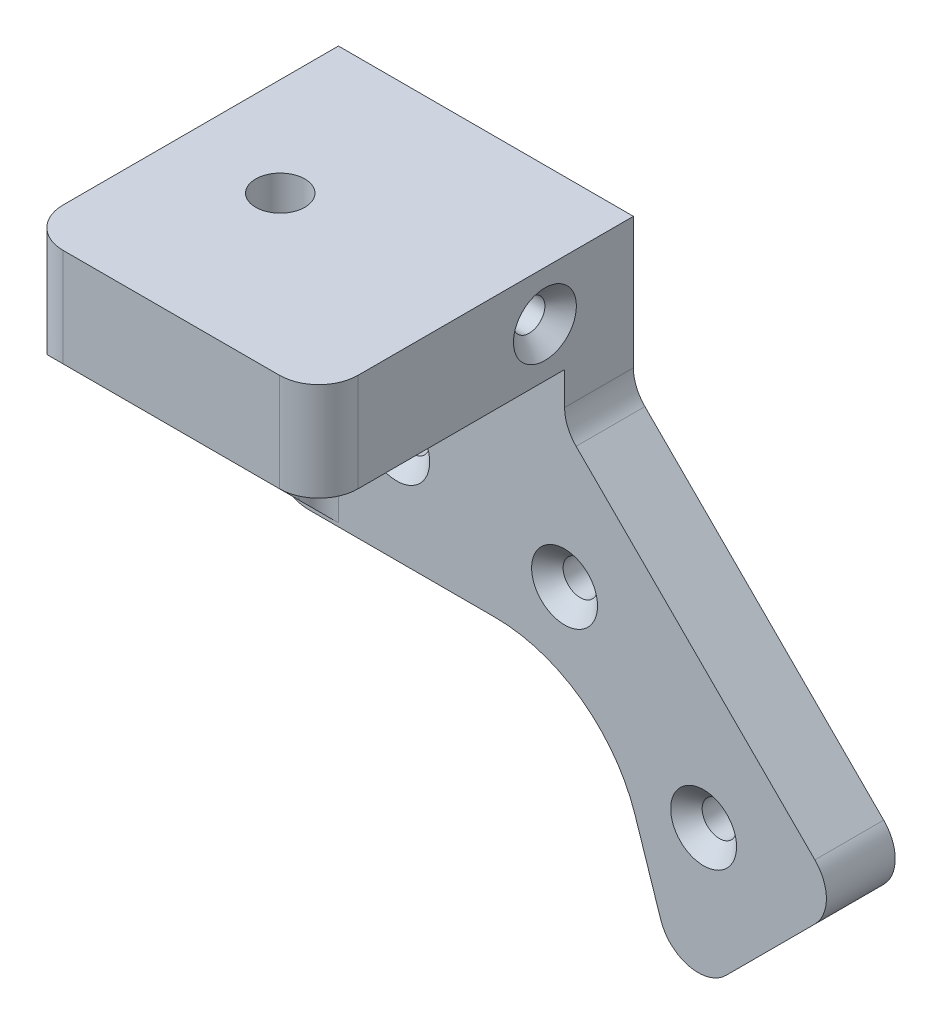
SolidWorks part; units mm, degrees
ref_plane "Front Plane" through (0, 0, 0) normal (0, 0, 1) x (1, 0, 0)
ref_plane "Top Plane" through (0, 0, 0) normal (0, 1, 0) x (1, 0, 0)
ref_plane "Right Plane" through (0, 0, 0) normal (1, 0, 0) x (0, 0, -1)
sketch "Sketch1" plane through (0, 0, 0) normal (0, 0, 1) x (1, 0, 0)
  line L0 (15, 27.5) -> (15, 12.5)
  line L5 (-15, 27.5) -> (15, 27.5)
  line L6 (-15, 27.5) -> (-15, -27.5)
  line L7 (-15, -27.5) -> (15, -27.5)
  line L9 (15, 12.5) -> (43.2843, -15.7843)
  line L10 (-15, -27.5) -> (15, 27.5) construction
  line L11 (43.2843, -15.7843) -> (23.2843, -35.7843)
  line L12 (23.2843, -35.7843) -> (15, -27.5)
  point P0 (0, 0)
  dimension "D1" = 45
  dimension "D2" = 55
  dimension "D3" = 30
  dimension "D4" = 40
  dimension "D5" = 15
extrude "Boss-Extrude1" add sketch "Sketch1" along normal blind 5 and the other way blind 2
sketch "Sketch3" plane through (0, 0, 5) normal (0, 0, 1) x (1, 0, 0)
  line L0 (15, 12.5) -> (15, 27.5) construction
  line L1 (-15, 27.5) -> (15, 27.5)
  line L2 (-15, 27.5) -> (-15, 17.5)
  line L3 (-15, 17.5) -> (15, 17.5)
  line L4 (15, 27.5) -> (15, 17.5)
  dimension "D1" = 10
extrude "Boss-Extrude2" add sketch "Sketch3" along normal blind 25
sketch "Sketch4" plane through (0, 27.5, 0) normal (0, 1, 0) x (1, 0, 0)
  line L0 (-15, -30) -> (-15, 2) construction
  line L1 (15, -30) -> (-15, -30) construction
  line L2 (15, -30) -> (15, -5) construction
  line L3 (15, -5) -> (-15, -5) construction
  line L4 (-15, -30) -> (-15, -5) construction
  line L5 (15, -30) -> (15, 2) construction
  line L6 (-15, 2) -> (15, 2) construction
  line L7 (-15, 2) -> (-15, 7) construction
  line L8 (-15, 7) -> (15, 7) construction
  line L9 (15, 2) -> (15, 7) construction
  line L10 (15, -20.575) -> (-15, -20.575) construction
  circle A0 centre (-5, -13.9175) radius 2.5
  circle A1 centre (-5, -13.9175) radius 6.6575 construction
  circle A2 centre (-5, -14.15) radius 6.425 construction
  dimension "D3" = 13.315
  dimension "D4" = 5
  dimension "D7" = 21.15
  dimension "D8" = 12.85
  dimension "D1" = 25
  dimension "D2" = 5
  dimension "D6" = 20
extrude "Cut-Extrude1" cut sketch "Sketch4" against normal through all
sketch "Sketch6" plane through (-15, 0, 0) normal (-1, 0, 0) x (0, 0, 1)
  line L0 (30, 17.5) -> (5, -7.5)
  line L1 (5, 17.5) -> (5, -27.5) construction
  dimension "D1" = 45
rib "Rib1" sketch "Sketch6" sketch "Sketch6" thickness 5 extrusion direction parallel to sketch draft on no parameters "D1"=5
sketch "Sketch7" plane through (0, 0, 5) normal (0, 0, 1) x (1, 0, 0)
  line L0 (22.1747, -18.1589) -> (26.8198, -32.2487)
  line L1 (-15, -7.8553) -> (7.9289, -7.8553)
  line L2 (-15, -7.8553) -> (-15, -27.5)
  line L3 (-15, -7.5) -> (-15, -27.5) construction
  line L4 (-15, -27.5) -> (15, -27.5) construction
  line L5 (15, 27.5) -> (-15, 27.5) construction
  line L6 (23.2843, -35.7843) -> (43.2843, -15.7843) construction
  line L7 (-15, -27.5) -> (23.2843, -35.7843)
  line L8 (23.2843, -35.7843) -> (26.8198, -32.2487)
  arc A0 (22.1747, -18.1589) -> (7.9289, -7.8553) centre (7.9289, -22.8553) ccw
  circle A1 centre (7.9289, -22.8553) radius 14 construction
  dimension "D1" = 1
  dimension "D2" = 5
extrude "Cut-Extrude2" cut sketch "Sketch7" against normal up to vertex (7 mm away) up to point (-15, -27.5, -2)
sketch "Sketch8" plane through (0, 17.5, 0) normal (0, -1, 0) x (-1, 0, 0)
  line L1 (0.2657, -13.9175) -> (2.6329, -18.0175)
  line L2 (2.6329, -18.0175) -> (7.3671, -18.0175)
  line L3 (7.3671, -18.0175) -> (9.7343, -13.9175)
  line L4 (9.7343, -13.9175) -> (7.3671, -9.8175)
  line L5 (7.3671, -9.8175) -> (2.6329, -9.8175)
  line L6 (2.6329, -9.8175) -> (0.2657, -13.9175)
  circle A0 centre (5, -13.9175) radius 4.1 construction
  dimension "D1" = 8.2
extrude "Cut-Extrude3" cut sketch "Sketch8" against normal blind 5
fillet "Fillet1" radius 4 2 edges at (-15, 22.5, 30) (15, 22.5, 30)
sketch "Sketch9" plane through (0, 0, 5) normal (0, 0, 1) x (1, 0, 0)
  line L0 (15, -1.6421) -> (22.0711, 5.4289) construction
  line L1 (43.2843, -15.7843) -> (15, 12.5) construction
  line L2 (29.1421, -15.7843) -> (36.2132, -8.7132) construction
  line L3 (26.8198, -32.2487) -> (43.2843, -15.7843) construction
  line L4 (15, 12.5) -> (-5.3553, -7.8553) construction
  line L5 (7.9289, -7.8553) -> (-15, -7.8553) construction
  line L6 (15, 12.5) -> (-15, 12.5) construction
  line L7 (-15, 13.5) -> (-15, -7.5) construction
  circle A0 centre (15, -1.6421) radius 1.75
  circle A1 centre (29.1421, -15.7843) radius 1.75
  circle A2 centre (-2.0711, 2.5) radius 1.75
  dimension "D1" = 3.5
  dimension "D5" = 5
  dimension "D2" = 10
  dimension "D3" = 10
  dimension "D4" = 20
  dimension "D6" = 10
extrude "Cut-Extrude4" cut sketch "Sketch9" against normal through all
chamfer "Chamfer1" distance 1.6 angle 45 3 edges at (30.8921, -15.7843, 5) (16.75, -1.6421, 5) (-0.3211, 2.5, 5)
fillet "Fillet2" radius 4 4 edges at (15, 12.5, 1.5) (43.2843, -15.7843, 1.5) (26.8198, -32.2487, 1.5) (-15, -7.8553, 1.5)
sketch "Sketch10" plane through (15, 0, 0) normal (1, 0, 0) x (0, 0, -1)
  line L0 (-7, 17.5) -> (-7, 27.5) construction
  line L1 (-26, 17.5) -> (-5, 17.5) construction
  line L2 (-26, 27.5) -> (2, 27.5) construction
  line L3 (2, 14.1569) -> (2, 27.5) construction
  circle A0 centre (-7, 22.5) radius 1.6
  dimension "D1" = 3.2
  dimension "D2" = 9
extrude "Cut-Extrude5" cut sketch "Sketch10" against normal through all
sketch "Sketch11" plane through (-15, 0, 0) normal (-1, 0, 0) x (0, 0, 1)
  line L1 (8.5877, 19.75) -> (10.1754, 22.5)
  line L2 (10.1754, 22.5) -> (8.5877, 25.25)
  line L3 (8.5877, 25.25) -> (5.4123, 25.25)
  line L4 (5.4123, 25.25) -> (3.8246, 22.5)
  line L5 (3.8246, 22.5) -> (5.4123, 19.75)
  line L6 (5.4123, 19.75) -> (8.5877, 19.75)
  circle A0 centre (7, 22.5) radius 2.75 construction
  dimension "D1" = 5.5
extrude "Cut-Extrude6" cut sketch "Sketch11" against normal blind 4
chamfer "Chamfer2" distance 1.6 angle 45 1 edges at (15, 24.1, 7)
fillet "Fillet3" radius 2 1 edges at (-10, 5, 5)
